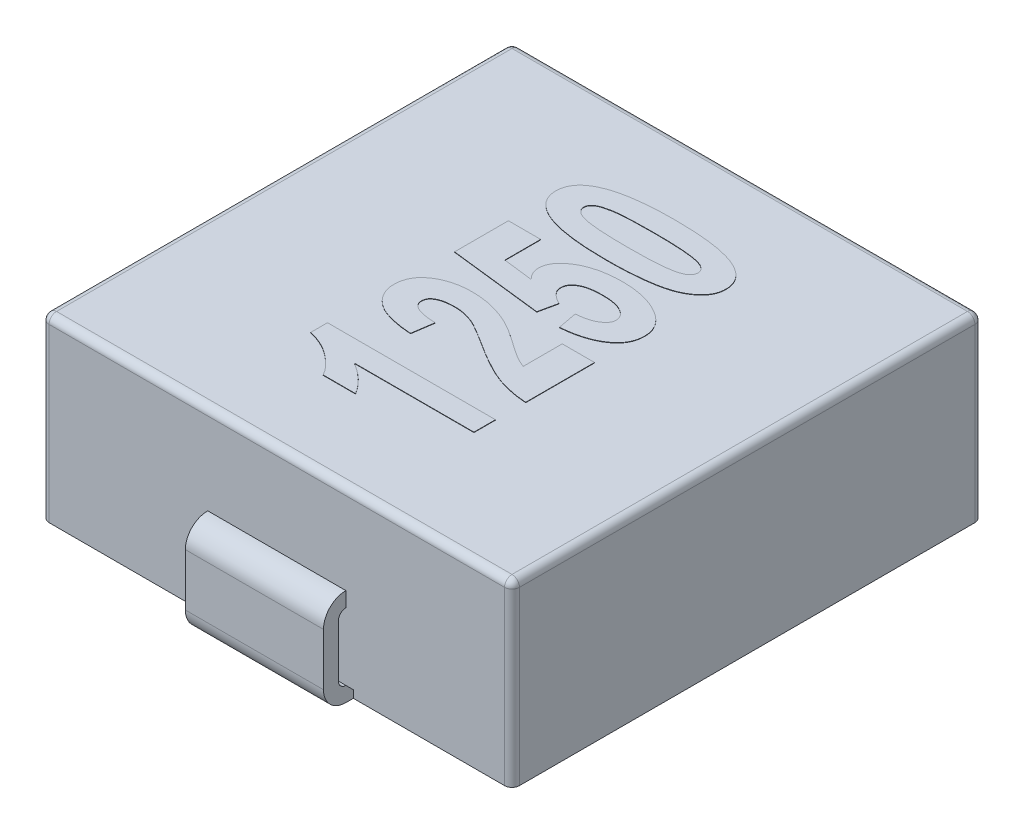
SolidWorks part; units mm, degrees
ref_plane "Спереди" through (0, 0, 0) normal (0, 0, 1) x (1, 0, 0)
ref_plane "Сверху" through (0, 0, 0) normal (0, 1, 0) x (1, 0, 0)
ref_plane "Справа" through (0, 0, 0) normal (1, 0, 0) x (0, 0, -1)
sketch "Эскиз1" plane through (0, 0, 0) normal (0, 1, 0) x (1, 0, 0)
  line L1 (-6.1, -6.3) -> (6.1, -6.3)
  line L2 (-6.3, -6.1) -> (-6.3, 6.1)
  line L3 (-6.1, 6.3) -> (6.1, 6.3)
  line L4 (6.3, -6.1) -> (6.3, 6.1)
  line L5 (-6.3, -6.3) -> (6.3, 6.3) construction
  line L6 (-6.3, 6.3) -> (6.3, -6.3) construction
  arc A0 (-6.1, -6.3) -> (-6.3, -6.1) centre (-6.1, -6.1) cw
  arc A1 (6.1, -6.3) -> (6.3, -6.1) centre (6.1, -6.1) ccw
  arc A2 (6.1, 6.3) -> (6.3, 6.1) centre (6.1, 6.1) cw
  arc A3 (-6.3, 6.1) -> (-6.1, 6.3) centre (-6.1, 6.1) cw
  point P0 (0, 0)
  dimension "D2" = 0.2
  dimension "D1" = 12.6
extrude "Бобышка-Вытянуть1" add sketch "Эскиз1" along normal blind 4.8
sketch "Эскиз2" plane through (0, 0, 0) normal (0, -1, 0) x (1, 0, 0)
  line L0 (-6.1, 6.3) -> (6.1, 6.3) construction
  line L1 (2.05, 6.3) -> (-2.05, 6.3)
  line L2 (2.05, 6.3) -> (2.05, 3.1)
  line L3 (2.05, 3.1) -> (-2.05, 3.1)
  line L4 (-2.05, 6.3) -> (-2.05, 3.1)
  line L5 (6.1, -6.3) -> (-6.1, -6.3) construction
  line L6 (2.05, -6.3) -> (-2.05, -6.3)
  line L7 (2.05, -6.3) -> (2.05, -3.1)
  line L8 (2.05, -3.1) -> (-2.05, -3.1)
  line L9 (-2.05, -6.3) -> (-2.05, -3.1)
  line L10 (-6.3, -6.1) -> (-6.3, 6.1) construction
  dimension "D1" = 4.25
  dimension "D2" = 4.1
  dimension "D3" = 3.2
extrude "Вырез-Вытянуть1" cut sketch "Эскиз2" against normal blind 0.2
sketch "Эскиз3" plane through (0, 0, 0) normal (1, 0, 0) x (0, 0, -1)
  line L0 (-6.3, 4.8) -> (-6.3, 0) construction
  line L1 (-6.9, 1.8) -> (-6.9, 0.4)
  line L2 (-6.3, -0.2) -> (-3.8, -0.2)
  line L3 (6.3, 4.8) -> (6.3, 0) construction
  line L4 (6.9, 1.8) -> (6.9, 0.4)
  line L5 (6.3, -0.2) -> (3.8, -0.2)
  line L6 (-6.3, 2.4) -> (6.3, 2.4) construction
  line L7 (-6.1, 0) -> (6.1, 0) construction
  arc A0 (-6.3, 2.4) -> (-6.9, 1.8) centre (-6.3, 1.8) ccw
  arc A1 (-6.9, 0.4) -> (-6.3, -0.2) centre (-6.3, 0.4) ccw
  arc A2 (6.3, 2.4) -> (6.9, 1.8) centre (6.3, 1.8) cw
  arc A3 (6.9, 0.4) -> (6.3, -0.2) centre (6.3, 0.4) cw
  dimension "D1" = 0.2
  dimension "D2" = 13.8
  dimension "D3" = 2.5
extrude "Вытянуть-Тонкостенный1" add sketch "Эскиз3" along normal mid plane 3.7 thin contours A0 L1 A1 L2 thin type one direction reverse wall 0.4
extrude "Вытянуть-Тонкостенный2" add sketch "Эскиз3<3>" along normal mid plane 3.7 thin contours A2 L4 A3 L5 thin type one direction wall 0.3
sketch "Эскиз3<3>" plane through (0, 0, 0) normal (1, 0, 0) x (0, 0, -1) same geometry as "Эскиз3"
fillet "Скругление1" radius 0.2 8 edges at (-6.2414, 4.8, 6.2414) (-6.3, 4.8, 0) (-6.2414, 4.8, -6.2414) (0, 4.8, -6.3) (6.2414, 4.8, -6.2414) (6.3, 4.8, 0) (6.2414, 4.8, 6.2414) (0, 4.8, 6.3)
sketch "Эскиз4" plane through (0, 4.8, 0) normal (0, 1, 0) x (1, 0, 0)
  line L0 (2.3, -4.3) -> (2.3, 6.3) construction
  line L1 (6.1, -6.3) -> (-6.1, -6.3) construction
  line L2 (6.3, 6.1) -> (6.3, -6.1) construction
  line L3 (-6.1, 6.3) -> (6.1, 6.3) construction
  text T0 "1250" font "Arial" height 4.5
  dimension "D1" = 2
  dimension "D2" = 4
extrude "Бобышка-Вытянуть2" add sketch "Эскиз4" along normal blind 0.01
equation "\"D1@Эскиз2\"=(\"D1@Эскиз1\"-\"D2@Эскиз2\")/2"
equation "\"D1@Вытянуть-Тонкостенный2\"=\"D1@Вытянуть-Тонкостенный1\""
